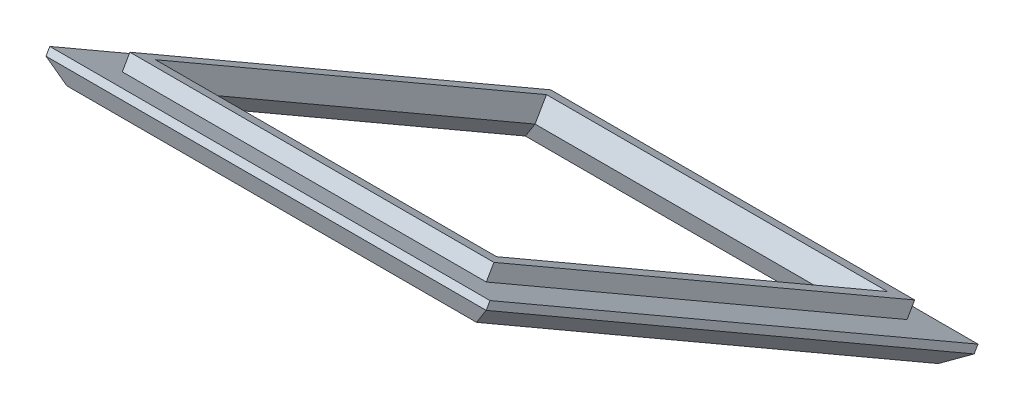
SolidWorks part; units mm, degrees
ref_plane "Front Plane" through (0, 0, 0) normal (1, 0, 0) x (0, 1, 0)
ref_plane "Top Plane" through (0, 0, 0) normal (0, 0, 1) x (0, 1, 0)
ref_plane "Right Plane" through (0, 0, 0) normal (0, 1, 0) x (-1, 0, 0)
sketch "Sketch1" plane through (0, -73.8743, 42.6513) normal (0, -0.866, 0.5) x (1, 0, 0)
  line L0 (-20.3754, 34.8073) -> (24.4246, 34.8073) construction
  line L1 (24.4246, 34.8073) -> (24.4246, 94.1073) construction
  line L2 (24.4246, 94.1073) -> (-20.3754, 94.1073) construction
  line L3 (-20.3754, 94.1073) -> (-20.3754, 34.8073) construction
  line L16 (-20.3754, 34.8073) -> (24.4246, 34.8073)
  line L17 (24.4246, 34.8073) -> (24.4246, 94.1073)
  line L18 (24.4246, 94.1073) -> (-20.3754, 94.1073)
  line L19 (-20.3754, 94.1073) -> (-20.3754, 34.8073)
  line L20 (-26.8754, 27.4573) -> (30.9246, 27.4573)
  line L21 (30.9246, 27.4573) -> (30.9246, 101.4573)
  line L22 (30.9246, 101.4573) -> (-26.8754, 101.4573)
  line L23 (-26.8754, 101.4573) -> (-26.8754, 27.4573)
  dimension "D1" = 6.5
  dimension "D2" = 7.35
  dimension "D3" = 7.35
  dimension "D4" = 6.5
extrude "Boss-Extrude1" add sketch "Sketch1" against normal blind 3
chamfer "Chamfer1" distance 2 angle 45 8 edges at (2.0246, -56.4706, 72.7953) (24.4246, -41.6456, 98.473) (2.0246, -26.8206, 124.1506) (-20.3754, -41.6456, 98.473) (2.0246, -60.1456, 66.4301) (30.9246, -41.6456, 98.473) (-26.8754, -41.6456, 98.473) (2.0246, -23.1456, 130.5159)
sketch "Sketch2" plane through (0, -71.2762, 41.1513) normal (0, 0.866, -0.5) x (-1, 0, 0)
  line L0 (20.3754, 94.1073) -> (20.3754, 34.8073) construction
  line L1 (-26.0246, 96.3573) -> (21.7754, 96.3573)
  line L2 (-26.0246, 96.3573) -> (-26.0246, 32.5573)
  line L3 (-26.0246, 32.5573) -> (21.7754, 32.5573)
  line L4 (21.7754, 96.3573) -> (21.7754, 32.5573)
  line L5 (20.3754, 34.8073) -> (-24.4246, 34.8073) construction
  line L6 (-24.4246, 34.8073) -> (-24.4246, 94.1073) construction
  line L7 (-24.4246, 94.1073) -> (20.3754, 94.1073) construction
  line L8 (20.3754, 94.1073) -> (20.3754, 34.8073)
  line L9 (20.3754, 34.8073) -> (-24.4246, 34.8073)
  line L10 (-24.4246, 34.8073) -> (-24.4246, 94.1073)
  line L11 (-24.4246, 94.1073) -> (20.3754, 94.1073)
  line L12 (-26.1246, 32.4573) -> (-26.1246, 96.4573) construction
  line L13 (21.8754, 96.4573) -> (21.8754, 32.4573) construction
  line L14 (-26.1246, 96.4573) -> (21.8754, 96.4573) construction
  line L15 (21.8754, 32.4573) -> (-26.1246, 32.4573) construction
  dimension "D1" = 0.1
  dimension "D2" = 0.1
  dimension "D3" = 0.1
  dimension "D4" = 0.1
extrude "Boss-Extrude2" add sketch "Sketch2" along normal up to surface (2 mm away)
